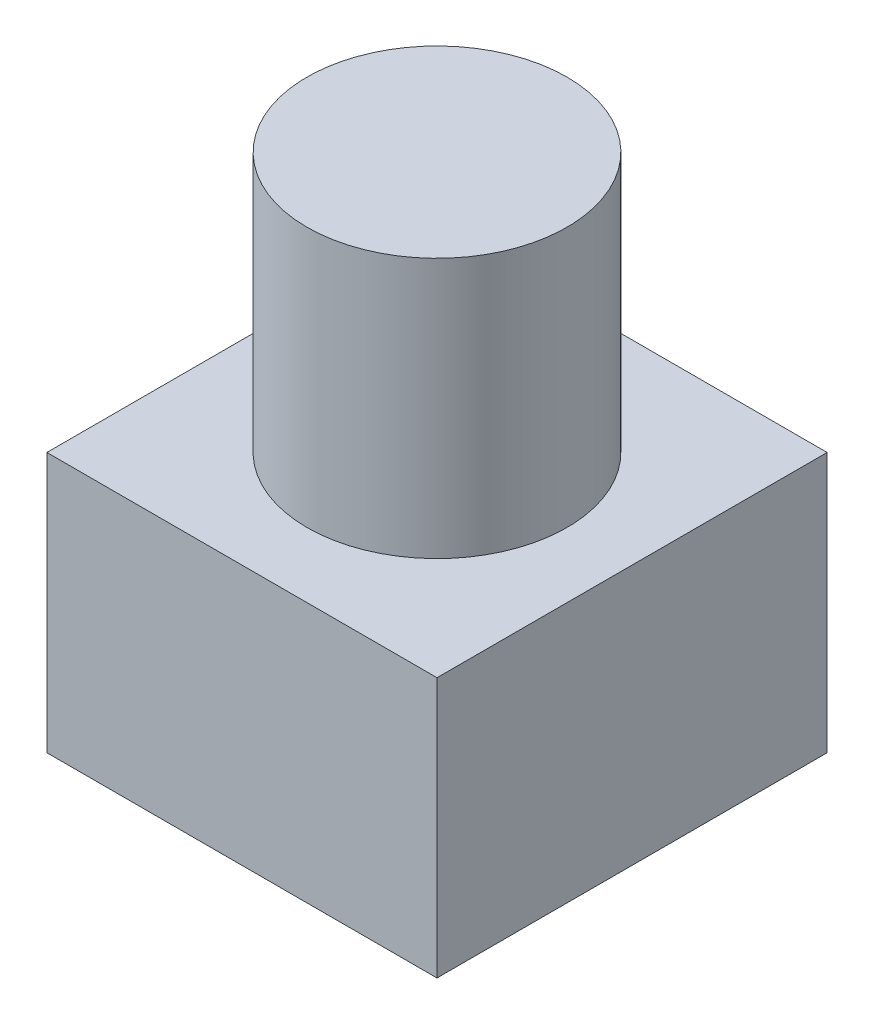
SolidWorks part; units mm, degrees
ref_plane "Płaszczyzna przednia" through (0, 0, 0) normal (0, 0, 1) x (1, 0, 0)
ref_plane "Płaszczyzna górna" through (0, 0, 0) normal (0, 1, 0) x (1, 0, 0)
ref_plane "Płaszczyzna prawa" through (0, 0, 0) normal (1, 0, 0) x (0, 0, -1)
sketch "Szkic2" plane through (0, 0, 0) normal (0, 1, 0) x (1, 0, 0)
  line L1 (-7.5, -7.5) -> (7.5, -7.5)
  line L2 (-7.5, -7.5) -> (-7.5, 7.5)
  line L3 (-7.5, 7.5) -> (7.5, 7.5)
  line L4 (7.5, -7.5) -> (7.5, 7.5)
  line L5 (-7.5, -7.5) -> (7.5, 7.5) construction
  line L6 (-7.5, 7.5) -> (7.5, -7.5) construction
  circle A0 centre (0, 0) radius 5
  dimension "D1" = 10
  dimension "D2" = 15
  dimension "D3" = 15
extrude "Dodanie-wyciągnięcie1" add sketch "Szkic2" along normal blind 20 contours A0
extrude "Dodanie-wyciągnięcie2" add sketch "Szkic2<3>" along normal blind 10 contours A0 region at (-7.2879, 0, 0)
sketch "Szkic2<3>" plane through (0, 0, 0) normal (0, 1, 0) x (1, 0, 0) same geometry as "Szkic2"
